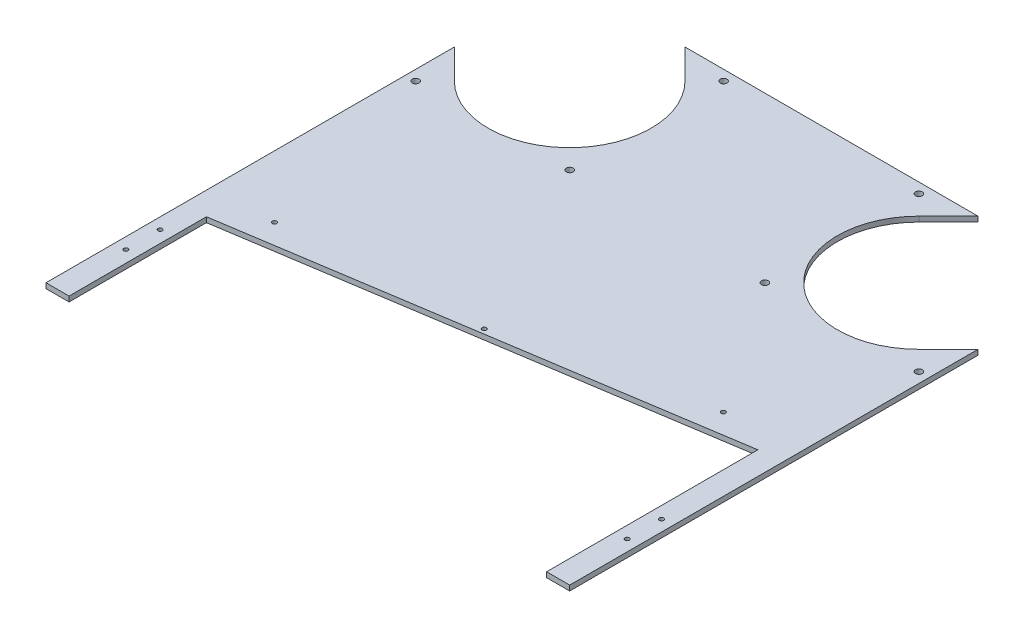
SolidWorks part; units mm, degrees
material "6061 Alloy"
ref_plane "Front Plane" through (0, 0, 0) normal (0, 0, 1) x (1, 0, 0)
ref_plane "Top Plane" through (0, 0, 0) normal (0, 1, 0) x (1, 0, 0)
ref_plane "Right Plane" through (0, 0, 0) normal (1, 0, 0) x (0, 0, -1)
sketch "Sketch1" plane through (0, 0, 0) normal (0, 1, 0) x (1, 0, 0)
  line L0 (0, 0) -> (0, 200)
  line L1 (0, 200) -> (305, 200)
  line L2 (305, 200) -> (305, 35.3098)
  line L3 (291.5711, 18.0458) -> (13.4289, -25)
  line L4 (0, 0) -> (0, -105)
  line L5 (0, -105) -> (13.4289, -105)
  line L6 (13.4289, -105) -> (13.4289, -25)
  line L7 (305, 35.3098) -> (305, -105)
  line L8 (305, -105) -> (291.5711, -105)
  line L9 (291.5711, -105) -> (291.5711, 18.0458)
  dimension "D1" = 305
  dimension "D2" = 81.203
  dimension "D3" = 200
  dimension "D4" = 13.4289
  dimension "D5" = 13.4289
  dimension "D6" = 105
  dimension "D7" = 305
  dimension "D8" = 80
sheet metal parameters "Sheet-Metal1" thickness 3 parameters "D1"=0.7366
base flange "Base-Flange1" sketch "Sketch1" thickness 3 reverse thickness direction no parameters "D1"=0.7366
hole_wizard "M3 Tapped Hole1" positions "Sketch6" profile "Sketch5" tap size "M3" standard "ISO"
sketch "Sketch6" plane through (0, 0, 0) normal (0, 1, 0) x (1, 0, 0)
  line L0 (0, 200) -> (0, -105) construction
  line L1 (305, -105) -> (305, 200) construction
  line L2 (0, -105) -> (13.4289, -105) construction
  line L3 (291.5711, -105) -> (305, -105) construction
  point P0 (6.5, -45)
  point P2 (6.5, -65)
  point P4 (298.5, -45)
  point P6 (298.5, -65)
  dimension "D1" = 6.5
  dimension "D3" = 6.5
  dimension "D5" = 20
  dimension "D6" = 20
  dimension "D7" = 40
  dimension "D8" = 40
sketch "Sketch5" plane through (6.5, 0, 45) normal (1, 0, 0) x (0, 0, 1)
  line L0 (0, 0) -> (0, 8.2511)
  line L1 (0, 8.2511) -> (1.25, 7.5)
  line L2 (1.25, 7.5) -> (1.25, 0)
  line L5 (1.25, 0) -> (0, 0)
  line L10 (0, 8.2511) -> (-1.25, 7.5) construction
  line L11 (0, -6.35) -> (0, 107.95) construction
  dimension "Tap Drill Dia." = 2.5
  dimension "Tap Drill Depth" = 7.5
  dimension "Drill Angle" = 118
cosmetic thread "Hole Thread1" parameters "D1"=3, "D2"=3
cosmetic thread "Hole Thread2" parameters "D1"=3, "D2"=3
cosmetic thread "Hole Thread3" parameters "D1"=3, "D2"=3
cosmetic thread "Hole Thread4" parameters "D1"=3, "D2"=3
hole_wizard "M3 Tapped Hole2" positions "Sketch10" profile "Sketch9" tap size "M3" standard "ISO"
sketch "Sketch10" plane through (0, 0, 0) normal (0, 1, 0) x (1, 0, 0)
  line L0 (13.4289, -11.5424) -> (290.1347, 31.2811) construction
  line L9 (13.4289, -25) -> (291.5711, 18.0458) construction
  line L10 (13.4289, -25) -> (13.4289, -11.5424) construction
  point P0 (36.1163, -8.0313)
  point P3 (150.8779, -0.6299)
  point P6 (262.508, 27.0056)
  dimension "D1" = 13.4576
  dimension "D2" = 280
  dimension "D3" = 115
  dimension "D4" = 115
sketch "Sketch9" plane through (36.1163, 0, 8.0313) normal (1, 0, 0) x (0, 0, 1)
  line L0 (0, 0) -> (0, 8.2511)
  line L1 (0, 8.2511) -> (1.25, 7.5)
  line L2 (1.25, 7.5) -> (1.25, 0)
  line L5 (1.25, 0) -> (0, 0)
  line L10 (0, 8.2511) -> (-1.25, 7.5) construction
  line L11 (0, -6.35) -> (0, 107.95) construction
  dimension "Tap Drill Dia." = 2.5
  dimension "Tap Drill Depth" = 7.5
  dimension "Drill Angle" = 118
cosmetic thread "Hole Thread5" parameters "D1"=3, "D2"=3
cosmetic thread "Hole Thread6" parameters "D1"=3, "D2"=3
cosmetic thread "Hole Thread7" parameters "D1"=3, "D2"=3
sketch "Sketch11" plane through (0, 0, 0) normal (0, 1, 0) x (1, 0, 0)
  line L0 (0, 132.8249) -> (17.2124, 115.6124)
  line L1 (0, 200) -> (0, -105) construction
  line L2 (17.2124, 115.6124) -> (0, 115.6124) construction
  line L3 (84.3876, 182.7876) -> (67.1751, 200)
  line L4 (305, 200) -> (0, 200) construction
  line L5 (220.6124, 182.7876) -> (237.8249, 200)
  line L6 (287.7876, 115.6124) -> (305, 132.8249)
  line L7 (305, -105) -> (305, 200) construction
  line L8 (287.7876, 115.6124) -> (305, 115.6124) construction
  line L9 (0, 132.8249) -> (0, 200)
  line L10 (0, 200) -> (67.1751, 200)
  circle A0 centre (50.8, 149.2) radius 47.5
  circle A1 centre (254.2, 149.2) radius 47.5
  circle A2 centre (95.6437, 194.0437) radius 1.9844
  circle A3 centre (5.9563, 104.3563) radius 1.9844
  circle A4 centre (95.6437, 104.3563) radius 1.9844
  circle A5 centre (209.3563, 104.3563) radius 1.9844
  circle A6 centre (299.0437, 104.3563) radius 1.9844
  circle A7 centre (209.3563, 194.0437) radius 1.9844
  line M10 (0, 200) -> (0, -105)
  line M16 (305, -105) -> (305, 200)
  line M17 (305, 200) -> (0, 200)
  dimension "D2" = 95
  dimension "D3" = 95
  dimension "D8" = 3.9688
  dimension "D9" = 3.9688
  dimension "D11" = 3.9688
  dimension "D15" = 3.9687
  dimension "D16" = 3.9687
  dimension "D19" = 3.9687
  dimension "D1" = 45
  dimension "D4" = 45
  dimension "D5" = 5.9563
  dimension "D6" = 89.6874
  dimension "D7" = 95.6437
  dimension "D10" = 5.9563
  dimension "D12" = 5.9563
  dimension "D13" = 95.6437
  dimension "D14" = 95.6437
  dimension "D17" = 5.9563
extrude "Cut-Extrude1" cut sketch "Sketch11" against normal through all contours A0 L3 L0 M17 M10 | A0 | A1 | A1 L6 L5 M16 M17 | A2 | A3 | A4 | A7 | A5 | A6 region at (1.1934, 0, -166.4124) region at (271.4124, 0, -198.8066) region at (50.8, 0, -149.2) region at (254.2, 0, -149.2) region at (95.6437, 0, -194.0437) region at (5.9563, 0, -104.3563) region at (95.6437, 0, -104.3563) region at (209.3563, 0, -104.3563) region at (299.0437, 0, -104.3563) region at (209.3563, 0, -194.0437) normal cut yes
flat pattern "Flat-Pattern1" [suppressed]
sketch "Bend-Lines1" plane through (0, 0, 0) normal (0, 1, 0) x (1, 0, 0)
sketch3d "Bounding-Box1" [suppressed]
  line L0 (-304.8, 200, 0) -> (0, 200, 0) construction
  line L1 (-304.8, 0, 0) -> (0, 0, 0) construction
  line L2 (-304.8, 200, 0) -> (-304.8, 0, 0) construction
  line L3 (0, 200, 0) -> (0, 0, 0) construction
equation "\"D5@Sketch1\"=\"D4@Sketch1\""
